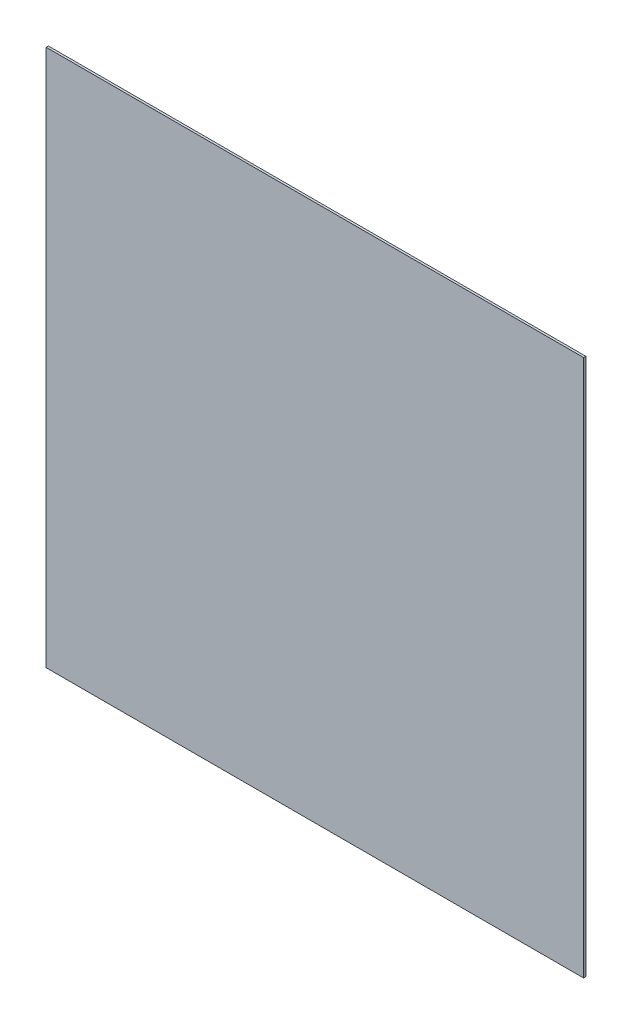
SolidWorks part; units mm, degrees
material "Mahogany"
ref_plane "Front Plane" through (0, 0, 0) normal (0, 0, 1) x (1, 0, 0)
ref_plane "Top Plane" through (0, 0, 0) normal (0, 1, 0) x (1, 0, 0)
ref_plane "Right Plane" through (0, 0, 0) normal (1, 0, 0) x (0, 0, -1)
sketch "Sketch1" plane through (0, 0, 0) normal (0, 0, 1) x (1, 0, 0)
  line L1 (-382.5, 382.5) -> (382.5, 382.5)
  line L2 (-382.5, 382.5) -> (-382.5, -382.5)
  line L3 (-382.5, -382.5) -> (382.5, -382.5)
  line L4 (382.5, 382.5) -> (382.5, -382.5)
  line L5 (-382.5, 382.5) -> (382.5, -382.5) construction
  line L6 (-382.5, -382.5) -> (382.5, 382.5) construction
  point P0 (0, 0)
  dimension "D1" = 765
  dimension "D2" = 765
extrude "Boss-Extrude1" add sketch "Sketch1" along normal blind 3.175
equation "\"W\"= 1700"
equation "\"L\"= 780"
equation "\"H\"= 780"
equation "\"ARM_BOLT_SPACING\"= 166"
equation "\"ARM_TO_WALL\"= 200"
equation "\"D1@Sketch1\"=\"L\"-15"
equation "\"D2@Sketch1\"=\"H\"-(15)"
